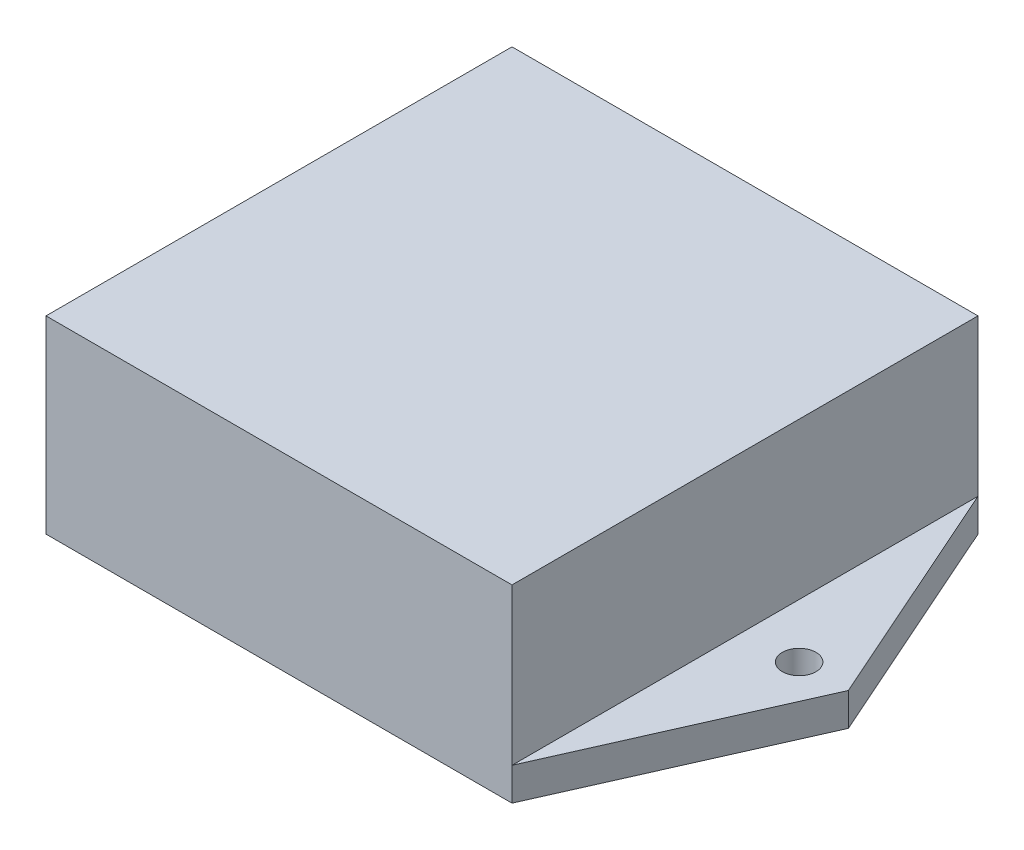
SolidWorks part; units mm, degrees
material "ABS"
ref_plane "Front Plane" through (0, 0, 0) normal (0, 0, 1) x (1, 0, 0)
ref_plane "Top Plane" through (0, 0, 0) normal (0, 1, 0) x (1, 0, 0)
ref_plane "Right Plane" through (0, 0, 0) normal (1, 0, 0) x (0, 0, -1)
sketch "Sketch1" plane through (0, 0, 0) normal (0, 1, 0) x (1, 0, 0)
  line L0 (14.2, 14.2) -> (20.5, 0)
  line L5 (-14.2, -14.2) -> (14.2, -14.2)
  line L6 (-14.2, -14.2) -> (-14.2, 14.2)
  line L7 (-14.2, 14.2) -> (14.2, 14.2)
  line L8 (14.2, -14.2) -> (14.2, 14.2)
  line L9 (-14.2, -14.2) -> (14.2, 14.2) construction
  line L10 (-14.2, 14.2) -> (14.2, -14.2) construction
  line L11 (20.5, 0) -> (14.2, -14.2)
  line L12 (-14.2, 14.2) -> (-20.5, 0)
  line L13 (-20.5, 0) -> (-14.2, -14.2)
  line L14 (0, 0) -> (0, 14.2) construction
  point P0 (0, 0)
  dimension "D1" = 28.4
  dimension "D2" = 41
extrude "Boss-Extrude1" add sketch "Sketch1" along normal blind 2 contours L5 L8 L7 L6 | L12 L13 L6 | L11 L0 L8 region at (0, 0, 0) region at (16.3, 0, 0) region at (-16.3, 0, 0)
extrude "Boss-Extrude2" add sketch "Sketch1<3>" along normal blind 11.52 contours L5 L8 L7 L6 region at (0, 0, 0)
sketch "Sketch1<3>" plane through (0, 0, 0) normal (0, 1, 0) x (1, 0, 0) same geometry as "Sketch1"
hole_wizard "M2.5 Tapped Hole1" positions "Sketch3" profile "Sketch4" tap size "M2.5" standard "ISO"
sketch "Sketch3" plane through (0, 2, 0) normal (0, 1, 0) x (1, 0, 0)
  line L0 (0, 14.2) -> (0, -14.2) construction
  line L1 (-14.2, -14.2) -> (14.2, -14.2) construction
  point P0 (-17.5, 0)
  point P2 (17.5, 0)
  point P16 (17.5, 0)
  dimension "D1" = 35
sketch "Sketch4" plane through (-17.5, 2, 0) normal (1, 0, 0) x (0, 0, 1)
  line L0 (0, 0) -> (0, 6.9659)
  line L1 (0, 6.9659) -> (1.025, 6.35)
  line L2 (1.025, 6.35) -> (1.025, 0)
  line L5 (1.025, 0) -> (0, 0)
  line L10 (0, 6.9659) -> (-1.025, 6.35) construction
  line L11 (0, -6.35) -> (0, 107.95) construction
  dimension "Tap Drill Dia." = 2.05
  dimension "Tap Drill Depth" = 6.35
  dimension "Drill Angle" = 118
cosmetic thread "Hole Thread1" parameters "D1"=5, "D2"=2.5
cosmetic thread "Hole Thread2" parameters "D1"=5, "D2"=2.5
